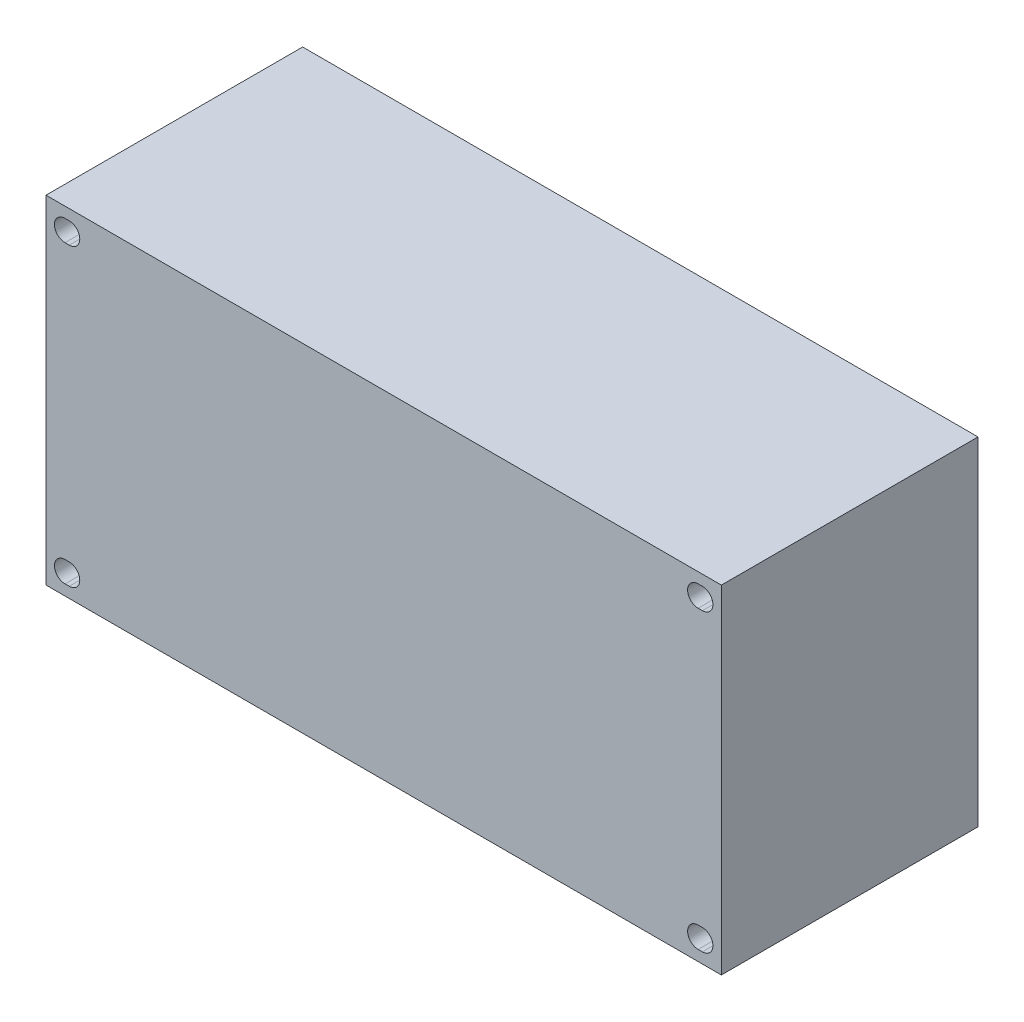
SolidWorks part; units mm, degrees
ref_plane "Front Plane" through (0, 0, 0) normal (0, 0, 1) x (1, 0, 0)
ref_plane "Top Plane" through (0, 0, 0) normal (0, 1, 0) x (1, 0, 0)
ref_plane "Right Plane" through (0, 0, 0) normal (1, 0, 0) x (0, 0, -1)
sketch "Sketch1" plane through (0, 0, 0) normal (0, 0, 1) x (1, 0, 0)
  line L1 (-50.8, -25.4) -> (50.8, -25.4)
  line L2 (-50.8, -25.4) -> (-50.8, 25.4)
  line L3 (-50.8, 25.4) -> (50.8, 25.4)
  line L4 (50.8, -25.4) -> (50.8, 25.4)
  line L5 (-50.8, -25.4) -> (50.8, 25.4) construction
  line L6 (-50.8, 25.4) -> (50.8, -25.4) construction
  point P0 (0, 0)
  dimension "D1" = 50.8
  dimension "D2" = 101.6
extrude "Boss-Extrude1" add sketch "Sketch1" along normal blind 38.608
sketch "Sketch4" plane through (0, 0, 38.608) normal (0, 0, 1) x (1, 0, 0)
  line L0 (50.8, 25.4) -> (-50.8, -25.4) construction
  line L1 (49.53, 28.72) -> (49.53, 15.73) construction
  line L2 (-47.625, 22.225) -> (47.625, 22.225) construction
  line L3 (-47.625, 22.225) -> (-47.625, -22.225) construction
  line L4 (-47.625, -22.225) -> (47.625, -22.225) construction
  line L5 (47.625, 22.225) -> (47.625, -22.225) construction
  line L6 (-47.625, 22.225) -> (47.625, -22.225) construction
  line L7 (-47.625, -22.225) -> (47.625, 22.225) construction
  line L8 (47.3075, 22.225) -> (47.9425, 22.225) construction
  line L9 (47.3075, 23.8125) -> (47.9425, 23.8125)
  line L10 (47.3075, 20.6375) -> (47.9425, 20.6375)
  line L11 (45.72, 16.7444) -> (45.72, 27.7056) construction
  arc A0 (47.3075, 23.8125) -> (47.3075, 20.6375) centre (47.3075, 22.225) ccw
  arc A1 (47.9425, 20.6375) -> (47.9425, 23.8125) centre (47.9425, 22.225) ccw
  point P4 (0, 0)
  point P12 (47.625, 22.225)
  point P20 (49.53, 22.225)
  point P23 (45.72, 22.225)
  dimension "D3" = 1.5875
  dimension "D1" = 44.45
  dimension "D2" = 95.25
  dimension "D4" = 3.81
extrude "Cut-Extrude1" cut sketch "Sketch4" against normal through all
mirror "Mirror1" about plane through (0, 0, 0) normal (0, 1, 0) of "Cut-Extrude1"
mirror "Mirror2" about plane through (0, 0, 0) normal (1, 0, 0) of "Mirror1"
